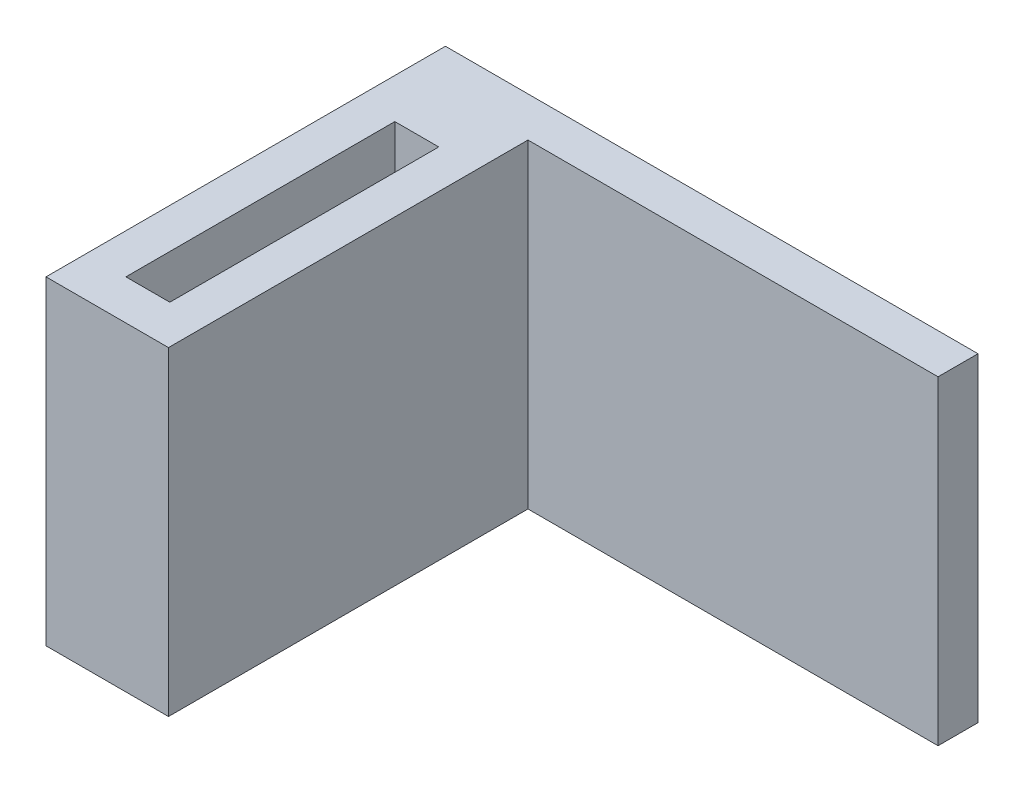
SolidWorks part; units mm, degrees
ref_plane "Front Plane" through (0, 0, 0) normal (0, 0, 1) x (1, 0, 0)
ref_plane "Top Plane" through (0, 0, 0) normal (0, 1, 0) x (1, 0, 0)
ref_plane "Right Plane" through (0, 0, 0) normal (1, 0, 0) x (0, 0, -1)
sketch "Sketch1" plane through (0, 0, 0) normal (0, 1, 0) x (1, 0, 0)
  line L0 (0, 0) -> (0, 15)
  line L1 (0, 15) -> (20, 15)
  line L2 (20, 15) -> (20, 13.5)
  line L3 (20, 13.5) -> (4.6, 13.5)
  line L4 (4.6, 13.5) -> (4.6, 0)
  line L5 (4.6, 0) -> (0, 0)
  line L7 (1.5, 1.5) -> (3.15, 1.5)
  line L8 (1.5, 1.5) -> (1.5, 11.6)
  line L9 (1.5, 11.6) -> (3.15, 11.6)
  line L10 (3.15, 1.5) -> (3.15, 11.6)
  dimension "D1" = 20
  dimension "D2" = 15
  dimension "D3" = 1.5
  dimension "D4" = 4.6
  dimension "D5" = 1.65
  dimension "D6" = 1.5
  dimension "D7" = 10.1
  dimension "D8" = 1.5
  dimension "D9" = 1.45
extrude "Boss-Extrude1" add sketch "Sketch1" along normal blind 1.5 contours L5 L0 L1 L2 L3 L4
extrude "Boss-Extrude2" add sketch "Sketch1<3>" along normal blind 12
sketch "Sketch1<3>" plane through (0, 0, 0) normal (0, 1, 0) x (1, 0, 0) same geometry as "Sketch1"
